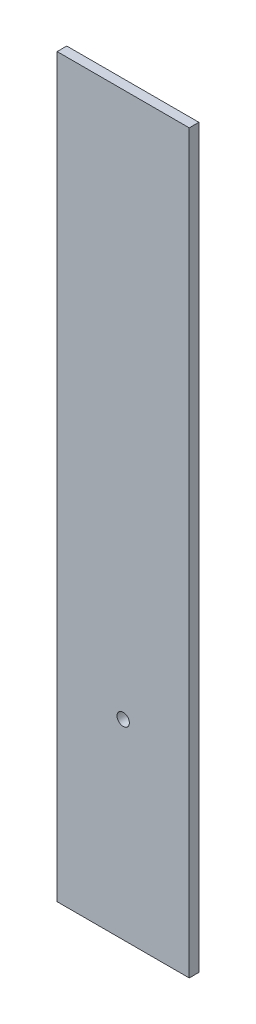
SolidWorks part; units mm, degrees
material "Beech"
ref_plane "Front" through (0, 0, 0) normal (0, 0, 1) x (1, 0, 0)
ref_plane "Top" through (0, 0, 0) normal (0, 1, 0) x (1, 0, 0)
ref_plane "Right" through (0, 0, 0) normal (1, 0, 0) x (0, 0, -1)
ref_axis "side-side" through (80.9, 0, 0) along (-1, 0, 0)
ref_axis "up-down" through (0, 50, 0) along (0, -1, 0)
ref_axis "front-back" through (0, 0, -80.9) along (0, 0, 1)
sketch "Sketch1" plane through (0, 0, 0) normal (0, 0, 1) x (1, 0, 0)
  line L0 (34, 352.2) -> (34, 397.2484) construction
  line L1 (-34, 394.9595) -> (34, 394.9595)
  line L2 (-34, 394.9595) -> (-34, 16)
  line L3 (-34, 16) -> (34, 16)
  line L4 (34, 394.9595) -> (34, 16)
  line L5 (34, 92.2187) -> (-19.1329, 16) construction
  circle A0 centre (0, 0) radius 31.1738 construction
  circle A1 centre (0, 114.3) radius 3.175
  point P4 (0, 0)
  point P12 (0, 0)
  dimension "D1" = 16
extrude "Boss-Extrude1" add sketch "Sketch1" along normal blind 4.953
